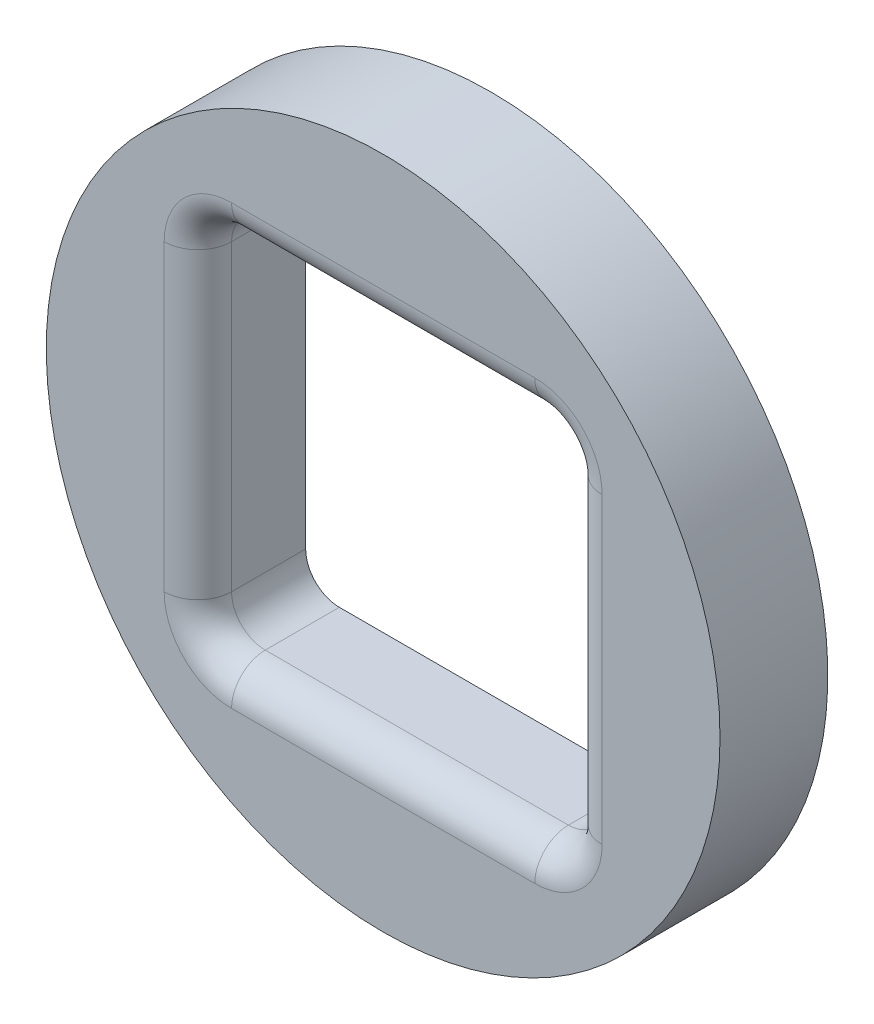
SolidWorks part; units mm, degrees
material "Custom Plastic"
ref_plane "Front Plane" through (0, 0, 0) normal (0, 0, 1) x (1, 0, 0)
ref_plane "Top Plane" through (0, 0, 0) normal (0, 1, 0) x (1, 0, 0)
ref_plane "Right Plane" through (0, 0, 0) normal (1, 0, 0) x (0, 0, -1)
sketch "Sketch1" plane through (0, 0, 0) normal (0, 0, 1) x (1, 0, 0)
  line L0 (-13.75, 13.75) -> (13.75, -13.75) construction
  line L1 (-13.75, 13.75) -> (13.75, 13.75)
  line L2 (-13.75, 13.75) -> (-13.75, -13.75)
  line L3 (-13.75, -13.75) -> (13.75, -13.75)
  line L4 (13.75, 13.75) -> (13.75, -13.75)
  circle A0 centre (0, 0) radius 25
  point P7 (0, 0)
  dimension "D2" = 50
  dimension "2.75" = 27.5
extrude "Boss-Extrude1" add sketch "Sketch1" along normal blind 55
sketch "Sketch2" plane through (0, 0, 0) normal (0, 0, -1) x (-1, 0, 0)
  circle A0 centre (0, 0) radius 25
  circle A1 centre (0, 0) radius 25
  circle A2 centre (0, 0) radius 25
  circle M2 centre (0, 0) radius 25
  line M3 (13.75, 13.75) -> (13.75, -13.75)
  line M4 (13.75, -13.75) -> (-13.75, -13.75)
  line M5 (-13.75, -13.75) -> (-13.75, 13.75)
  line M6 (-13.75, 13.75) -> (13.75, 13.75)
  dimension "D1" = 0
extrude "Boss-Extrude2" add sketch "Sketch2" along normal blind 5 contours M2 M6 M3 M4 M5 | M3 M6 M5 M4 region at (24.2929, 0, 0) region at (0, 0, 0)
sketch "Sketch3" plane through (0, 0, -5) normal (0, 0, -1) x (-1, 0, 0)
  line L1 (0, 25) -> (25, 25)
  line L2 (0, 25) -> (0, -25)
  line L3 (0, -25) -> (25, -25)
  line L4 (25, 25) -> (25, -25)
  circle A0 centre (0, 0) radius 25 construction
extrude "Boss-Extrude3" add sketch "Sketch3" along normal blind 80
ref_plane "Plane1" through (0, 0, -5) normal (0, 0, 1) x (1, 0, 0)
fillet "Fillet1" radius 2.5 4 edges at (-13.75, 13.75, 27.5) (13.75, 13.75, 27.5) (-13.75, -13.75, 27.5) (13.75, -13.75, 27.5)
fillet "Fillet2" radius 2.5 1 edges at (13.75, 0, 55) type face fillet first side face at (25, 0, 55) second side face at (13.75, 0, 27.5)
ref_plane "Plane2" through (-50, 0, 0) normal (-1, 0, 0) x (0, 0, 1)
sketch "Sketch18" plane through (0, 0, -5) normal (0, 0, 1) x (1, 0, 0)
  line L0 (0, -25) -> (-25, -25)
  line L1 (-25, 0) -> (-25, 25)
  line L2 (-25, -25) -> (0, -25)
  line L3 (-25, 0) -> (-25, -25)
  line L4 (-25, -25) -> (0, -25)
  line L5 (-25, 0) -> (-25, -25)
  line L6 (-25, 25) -> (0, 25)
  arc A1 (-25, 0) -> (0, -25) centre (0, 0) ccw
  arc A2 (-25, 0) -> (0, -25) centre (0, 0) ccw
  circle A3 centre (0, 0) radius 25
  circle A4 centre (0, 0) radius 25
  line M5 (-25, 25) -> (-25, 0)
  arc M6 (-25, 0) -> (0, 25) centre (0, 0) cw
  line M7 (0, 25) -> (-25, 25)
  dimension "D1" = 0
  dimension "D2" = 0
sketch "Sketch21" plane through (0, 0, 0) normal (1, 0, 0) x (0, 0, -1)
  line L0 (24.7, 10.15) -> (79, 10.15)
  line L1 (79, 10.15) -> (79, -10.15)
  line L2 (79, -10.15) -> (24.7, -10.15)
  line L3 (24.7, -10.15) -> (24.7, 10.15)
  line L6 (85, 25) -> (85, -25) construction
  line L7 (51.85, -10.15) -> (51.85, -25)
  line L8 (85, -25) -> (5, -25) construction
  line L9 (51.85, 10.15) -> (51.85, 25)
  line L10 (85, 25) -> (5, 25) construction
  dimension "D1" = 6
  dimension "D2" = 54.3
  dimension "D3" = 20.3
extrude "Cut-Extrude1" cut sketch "Sketch21" against normal blind 11.3 contours L3 L0 L1 L2
sketch "Sketch22" plane through (0, 0, 0) normal (1, 0, 0) x (0, 0, -1)
  line L0 (31.55, 10.15) -> (71.85, 10.15)
  line L1 (24.7, 10.15) -> (79, 10.15) construction
  line L2 (71.85, 10.15) -> (71.85, -10.15)
  line L3 (79, -10.15) -> (24.7, -10.15) construction
  line L4 (71.85, -10.15) -> (31.55, -10.15)
  line L5 (31.55, 10.15) -> (31.55, -10.15)
  line M9 (79, -10.15) -> (24.7, -10.15)
  line M11 (24.7, 10.15) -> (79, 10.15)
  dimension "D1" = 40.3
extrude "Cut-Extrude2" cut sketch "Sketch22" against normal through all contours L5 L2 M11 M9 region at (0, 0, -51.7)
extrude "Cut-Extrude3" cut sketch "Sketch18" against normal through all contours A2 L5 L0 | M7 M5 M6 region at (-19.4158, -19.4158, -5) region at (-19.4158, 19.4158, -5)
sketch "Sketch23" plane through (0, 0, 0) normal (1, 0, 0) x (0, 0, -1)
  line L0 (27.85, 5.25) -> (27.85, -5.25) construction
  line L1 (27.85, -5.25) -> (75.85, -5.25) construction
  line L2 (75.85, -5.25) -> (75.85, 5.25) construction
  line L3 (75.85, 5.25) -> (27.85, 5.25) construction
  circle A0 centre (75.85, 5.25) radius 2.15
  circle A1 centre (75.85, -5.25) radius 2.15
  circle A3 centre (27.85, 5.25) radius 2.15
  circle A4 centre (27.85, -5.25) radius 2.15
  dimension "D1" = 4.3
extrude "Cut-Extrude4" cut sketch "Sketch23" against normal through all contours A4 | A0 | A1 | A3 region at (0, 5.25, -75.85) region at (0, -5.25, -75.85) region at (0, -5.25, -27.85)
ref_plane "Plane3" through (0, 0, -51.7) normal (0, 0, -1) x (-1, 0, 0)
sketch "Sketch24" plane through (0, 0, -51.7) normal (0, 0, -1) x (-1, 0, 0)
  line L0 (13.3, 10.15) -> (13.3, -10.15)
  line L7 (22.8468, 10.15) -> (11.3, 10.15)
  line L8 (11.3, 10.15) -> (11.3, -10.15)
  line L9 (11.3, -10.15) -> (22.8468, -10.15)
  line L13 (22.8468, 10.15) -> (13.3, 10.15)
  line L15 (13.3, -10.15) -> (22.8468, -10.15)
  arc A2 (22.8468, -10.15) -> (22.8468, 10.15) centre (0, 0) ccw
  arc A4 (22.8468, -10.15) -> (22.8468, 10.15) centre (0, 0) ccw
  dimension "D1" = 0
  dimension "D2" = 13.3
extrude "Cut-Extrude7" cut sketch "Sketch24" against normal mid plane 55
sketch "Sketch25" plane through (0, 0, 0) normal (1, 0, 0) x (0, 0, -1)
  line L0 (5, 25) -> (-55, 25) construction
  line L1 (-47, 25) -> (85, 25)
  line L2 (-47, 25) -> (-47, -25)
  line L3 (-47, -25) -> (85, -25)
  line L4 (85, 25) -> (85, -25)
  line L5 (-55, 25) -> (-55, -25) construction
  dimension "D1" = 8
extrude "Cut-Extrude8" cut sketch "Sketch25" against normal through all both and the other way through all
